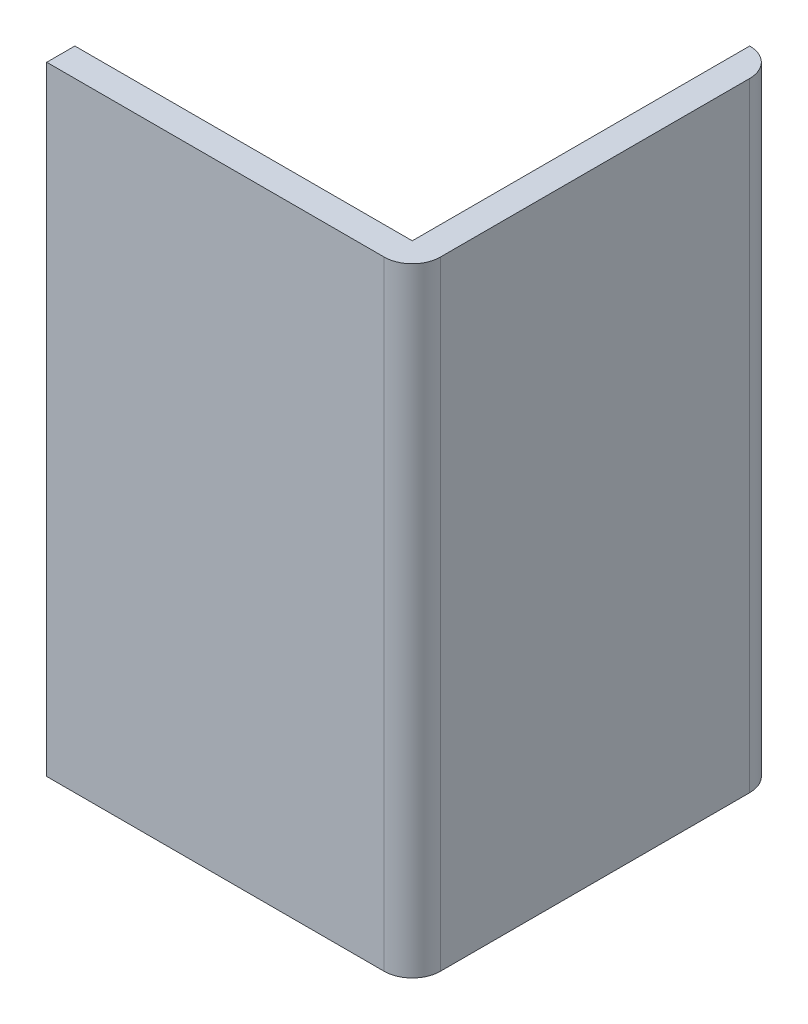
SolidWorks part; units mm, degrees
ref_plane "Front Plane" through (0, 0, 0) normal (0, 0, 1) x (1, 0, 0)
ref_plane "Top Plane" through (0, 0, 0) normal (0, 1, 0) x (1, 0, 0)
ref_plane "Right Plane" through (0, 0, 0) normal (1, 0, 0) x (0, 0, -1)
sketch "Sketch1" plane through (0, 0, 0) normal (0, 0, 1) x (1, 0, 0)
  line L1 (0, 0) -> (1.3, 0)
  line L2 (0, 0) -> (0, 2.2)
  line L3 (0, 2.2) -> (1.3, 2.2)
  line L4 (1.3, 0) -> (1.3, 2.2)
  dimension "D1" = 2.2
  dimension "D2" = 1.3
extrude "Boss-Extrude1" add sketch "Sketch1" along normal blind 0.1
sketch "Sketch2" plane through (0, 0, 0) normal (0, 0, -1) x (-1, 0, 0)
  line L0 (-1.3, 2.2) -> (0, 2.2) construction
  line L1 (-1.3, 0) -> (-1.2, 0)
  line L2 (-1.3, 0) -> (-1.3, 2.2)
  line L3 (-1.3, 2.2) -> (-1.2, 2.2)
  line L4 (-1.2, 0) -> (-1.2, 2.2)
  dimension "D1" = 0.1
extrude "Boss-Extrude2" add sketch "Sketch2" along normal blind 1.2
fillet "Fillet1" radius 0.1 1 edges at (1.3, 1.1, -1.2)
fillet "Fillet2" radius 0.1 1 edges at (1.3, 1.1, 0.1)
